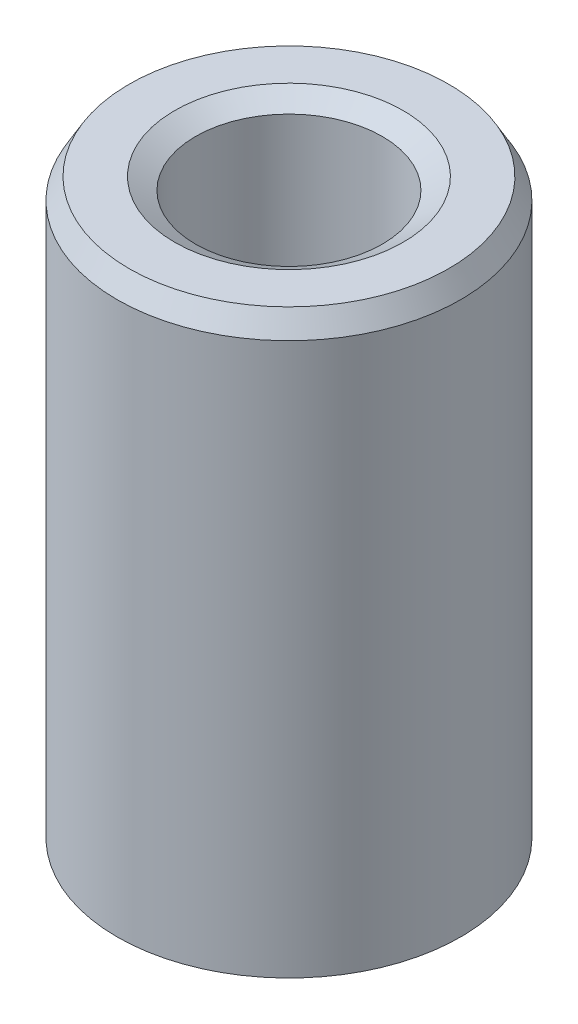
SolidWorks part; units mm, degrees
ref_plane "Front Plane" through (0, 0, 0) normal (0, 0, 1) x (1, 0, 0)
ref_plane "Top Plane" through (0, 0, 0) normal (0, 1, 0) x (1, 0, 0)
ref_plane "Right Plane" through (0, 0, 0) normal (1, 0, 0) x (0, 0, -1)
sketch "Sketch1" plane through (0, 0, 0) normal (0, 1, 0) x (1, 0, 0)
  circle A0 centre (0, 0) radius 32.5
  dimension "SLEEVE_OD" = 65
extrude "Boss-Extrude1" add sketch "Sketch1" along normal blind 110.6098
sketch "Sketch2" plane through (0, 0, 0) normal (0, 1, 0) x (1, 0, 0)
  circle A0 centre (0, 0) radius 17.66
  dimension "BORE_D" = 35.32
extrude "Cut-Extrude1" cut sketch "Sketch2" along normal through all
chamfer "Chamfer1" distance 3.9395 angle 30 4 edges at (0, 110.6098, 17.66) (0, 0, 17.66) (0, 0, 32.5) (0, 110.6098, 32.5) first distance on face at (0, 110.6098, 17.66) first distance on face at (0, 0, 17.66) first distance on face at (0, 110.6098, 32.5)
